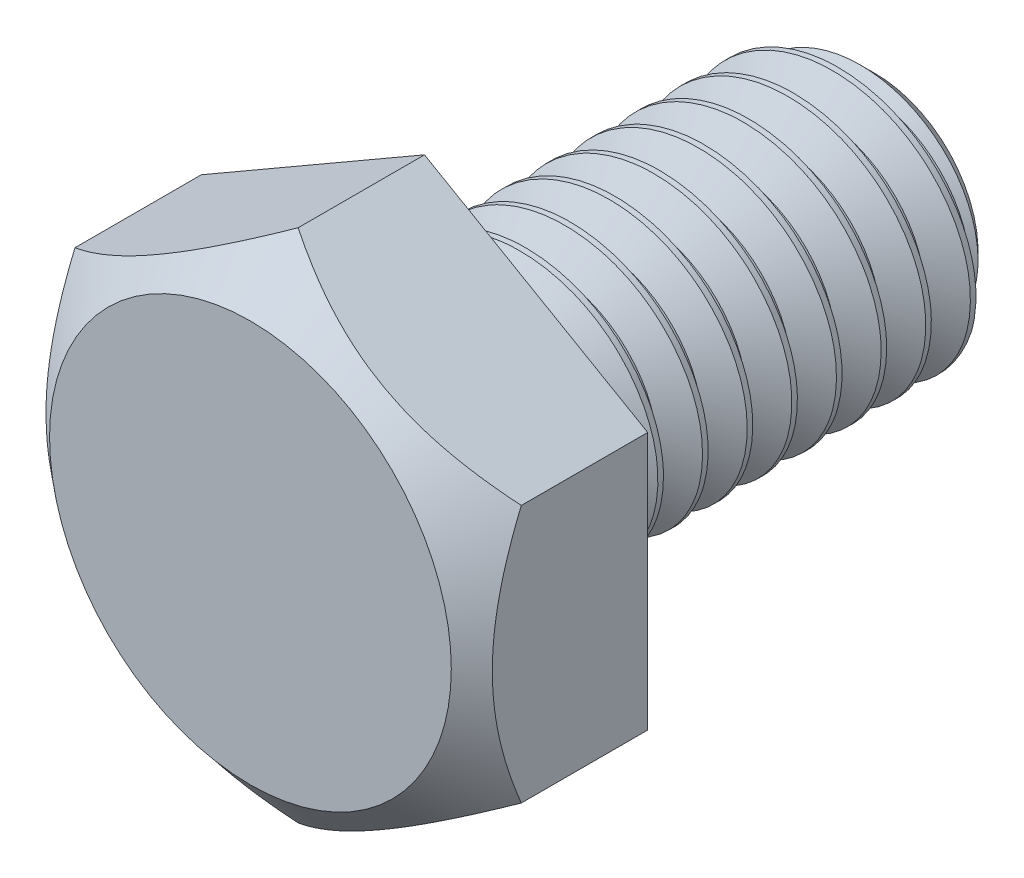
SolidWorks part; units mm, degrees
ref_plane "Front Plane" through (0, 0, 0) normal (0, 0, 1) x (1, 0, 0)
ref_plane "Top Plane" through (0, 0, 0) normal (0, 1, 0) x (1, 0, 0)
ref_plane "Right Plane" through (0, 0, 0) normal (1, 0, 0) x (0, 0, -1)
sketch "Sketch1" plane through (0, 0, 0) normal (1, 0, 0) x (0, 0, -1)
  line L0 (0, 0) -> (10, 0) construction
  line L1 (0, 0) -> (-4, 0) construction
  line L2 (10, 3) -> (10, -3) construction
  line L3 (-4, 5) -> (-4, -5) construction
  line L4 (0, 5) -> (0, -5) construction
  line L5 (9.9375, 3.1083) -> (10.9375, 3.1083) construction
  line L6 (10.9375, 3.1083) -> (10.4375, 2.2422) construction
  line L7 (10.4375, 2.2422) -> (9.9375, 3.1083) construction
  line L8 (9.9687, 3.0541) -> (10.9062, 3.0541) construction
  line L9 (10, 3) -> (10.875, 3) construction
  line L10 (10.375, 2.3505) -> (10.5, 2.3505) construction
  line L11 (10.4375, 2.3505) -> (10.4375, 2.2422) construction
  line L12 (10.4375, 3) -> (10.4375, 3.1083) construction
  point P6 (10, 0)
  point P10 (-4, 0)
  point P12 (0, 0)
  point P18 (6.5, -3)
  point P25 (10.4375, 3.0541)
  dimension "Thread Size" = 6
  dimension "Head Width" = 10
  dimension "Head Height" = 4
  dimension "Length" = 10
  dimension "D1" = 60
  dimension "Thread Pitch" = 1
  dimension "D2" = 0.125
  dimension "D3" = 3.5
sketch "Sketch2" plane through (0, 0, 0) normal (1, 0, 0) x (0, 0, -1)
  line L0 (10, 0) -> (0, 0)
  line L1 (10, 3) -> (10, -3) construction
  line L2 (0, 0) -> (0, 3)
  line L3 (0, 5) -> (0, -5) construction
  line L4 (0, 3) -> (9.3, 3)
  line L5 (9.3, 3) -> (10, 2.3)
  line L6 (10, 2.3) -> (10, 0)
  dimension "D1" = 0.7
  dimension "D2" = 45
revolve "Revolve1" add sketch "Sketch2" angle 360 about L0
sketch "Sketch3" plane through (0, 0, 0) normal (0, 0, 1) x (1, 0, 0)
  line L1 (0, 5.7735) -> (-5, 2.8868)
  line L2 (-5, 2.8868) -> (-5, -2.8868)
  line L3 (-5, -2.8868) -> (0, -5.7735)
  line L4 (0, -5.7735) -> (5, -2.8868)
  line L5 (5, -2.8868) -> (5, 2.8868)
  line L6 (5, 2.8868) -> (0, 5.7735)
  circle A0 centre (0, 0) radius 5 construction
extrude "Boss-Extrude1" add sketch "Sketch3" along normal up to vertex (4 mm away) up to point (0, 0, 4)
sketch "Sketch4" plane through (0, 0, 4) normal (0, 0, 1) x (1, 0, 0)
  circle A0 centre (0, 0) radius 4.5
  dimension "D1" = 9
extrude "Cut-Extrude1" cut sketch "Sketch4" against normal through all draft 50 flip side to cut
sketch "Sketch9" plane through (0, 0, 0) normal (0, 0, -1) x (-1, 0, 0)
  circle A0 centre (0, 0) radius 4.75
  circle A1 centre (0, 0) radius 5.7735
  dimension "D1" = 9.5
extrude "Cut-Extrude2" cut sketch "Sketch9" against normal blind 0.1
sketch "Sketch10" plane through (0, 0, 0) normal (1, 0, 0) x (0, 0, -1)
  line L0 (0, 5.7735) -> (0, -5.7735) construction
  line L1 (0, 0) -> (10, 0) construction
  point P3 (0, 0)
split "Split1" bodies to split 112 resulting bodies 108 109 split by face at (-3, 0, 0)
sketch "Sketch6" plane through (0, 0, 0) normal (1, 0, 0) x (0, 0, -1)
  line L0 (9.9687, 3.0541) -> (10.9062, 3.0541)
  line L1 (10.9062, 3.0541) -> (10.5, 2.3505)
  line L2 (10.5, 2.3505) -> (10.375, 2.3505)
  line L3 (10.375, 2.3505) -> (9.9687, 3.0541)
sketch "Sketch7" plane through (0, 0, -10) normal (0, 0, -1) x (-1, 0, 0)
  circle A0 centre (0, 0) radius 3
curve "Helix/Spiral1" pitch 1 height 11 radius 3 centre (0, 0, -10) axis (0, 0, 1) start towards (0, 1, 0)
sweep "Cut-Sweep1" cut profiles "Sketch6" path "Helix/Spiral1" align with end faces yes
sketch "Sketch8" plane through (0, 0, 0) normal (0, 0, -1) x (-1, 0, 0)
  circle A0 centre (0, 0) radius 3
extrude "Boss-Extrude2" add sketch "Sketch8" along normal blind 3 draft 20
equation "\"D2@Sketch1\" = \"Thread Pitch@Sketch1\" / 8"
equation "\"D3@Sketch1\" = \"Thread Pitch@Sketch1\" * 3.5"
equation "\"D1@Sketch2\" = \"Thread Pitch@Sketch1\" * .7"
equation "\"D1@Sketch4\"=\"Head Width@Sketch1\"*.9"
equation "\"D3@Helix/Spiral1\" = \"Length@Sketch1\" + \"Thread Pitch@Sketch1\""
equation "\"D4@Helix/Spiral1\" = \"Thread Pitch@Sketch1\""
equation "\"D1@Boss-Extrude2\" = \"Thread Pitch@Sketch1\" * 3"
equation "\"D1@Sketch9\"=\"Head Width@Sketch1\"*.95"
equation "\"D1@Cut-Extrude2\"=\"Head Height@Sketch1\"*.025"
